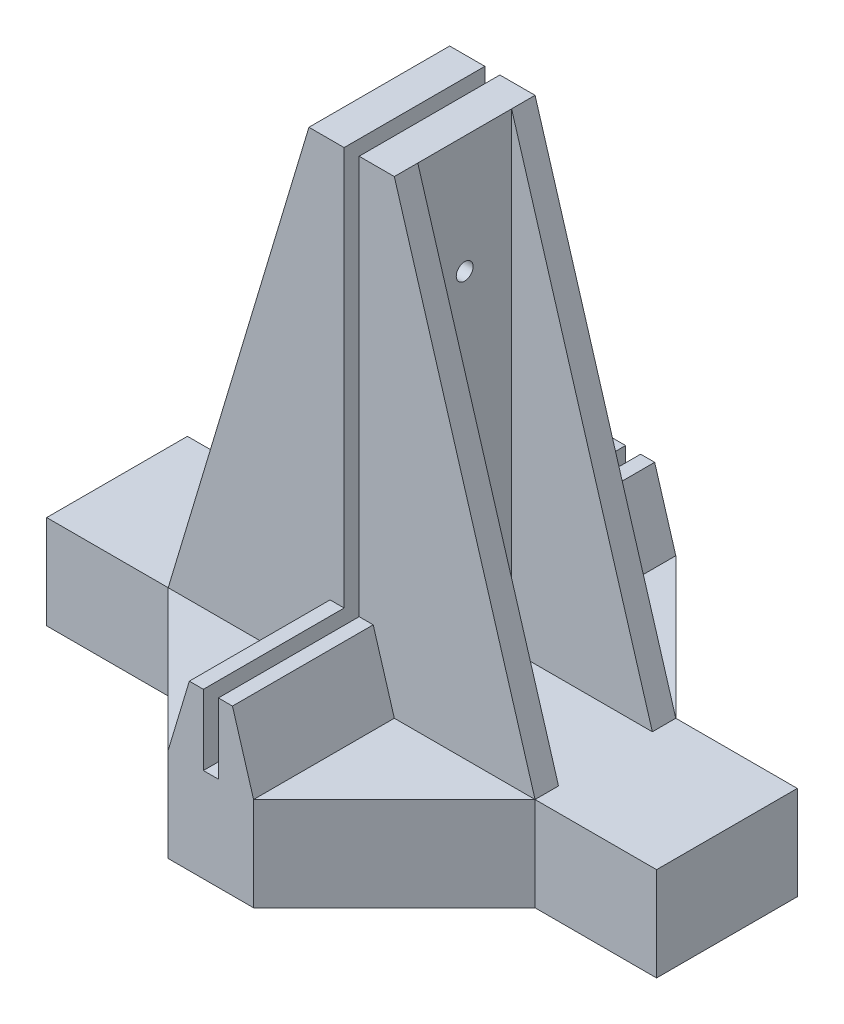
SolidWorks part; units mm, degrees
ref_plane "Front Plane" through (0, 0, 0) normal (0, 0, 1) x (1, 0, 0)
ref_plane "Top Plane" through (0, 0, 0) normal (0, 1, 0) x (1, 0, 0)
ref_plane "Right Plane" through (0, 0, 0) normal (1, 0, 0) x (0, 0, -1)
sketch "Sketch1" plane through (0, 0, 0) normal (0, 0, 1) x (1, 0, 0)
  line L0 (0, 0) -> (65, 0)
  line L1 (41.25, 0) -> (-41.25, 0) construction
  line L2 (65, 0) -> (65, 20)
  line L3 (65, 20) -> (9.1, 20)
  line L4 (9.1, 20) -> (9.1, 120)
  line L5 (9.1, 120) -> (1.6, 120)
  line L6 (1.6, 120) -> (1.6, 20)
  line L7 (1.6, 20) -> (-1.6, 20)
  line L8 (-1.6, 20) -> (-1.6, 120)
  line L9 (-1.6, 120) -> (-9.1, 120)
  line L10 (-9.1, 120) -> (-9.1, 20)
  line L11 (-9.1, 20) -> (-65, 20)
  line L12 (-65, 20) -> (-65, 0)
  line L13 (-65, 0) -> (0, 0)
  dimension "D1" = 65
  dimension "D2" = 20
  dimension "D3" = 55.9
  dimension "D4" = 100
  dimension "D5" = 7.5
  dimension "D6" = 3.2
  dimension "D7" = 130
  dimension "D8" = 7.5
extrude "Boss-Extrude3" add sketch "Sketch1" along normal blind 30
sketch "Sketch3" plane through (9.1, 0, 0) normal (1, 0, 0) x (0, 0, -1)
  line L0 (-30, 120) -> (0, 120) construction
  line L3 (-30, 20) -> (0, 20) construction
  circle A0 centre (-15, 95) radius 1.8
  circle A1 centre (-15, 45) radius 1.8
  point P0 (-15, 120)
  point P8 (0, 0)
  point P11 (0, 0)
  point P14 (0, 0)
  dimension "D3" = 3.6
  dimension "D2" = 3.6
  dimension "D4" = 25
  dimension "D1" = 50
extrude "Cut-Extrude1" cut sketch "Sketch3" against normal blind 161 and the other way blind 88
sketch "Sketch4" plane through (0, 0, 0) normal (0, 0, 1) x (1, 0, 0)
  line L0 (9.1, 120) -> (39.1, 20)
  line L1 (65, 20) -> (9.1, 20) construction
  line L2 (39.1, 20) -> (9.1, 20)
  line L3 (9.1, 20) -> (9.1, 120)
  line L4 (0, -1000) -> (0, 49000) construction
  line L6 (-9.1, 20) -> (-9.1, 120)
  line L7 (-39.1, 20) -> (-9.1, 20)
  line L8 (-9.1, 120) -> (-39.1, 20)
  dimension "D1" = 30
extrude "Boss-Extrude4" add sketch "Sketch4" along normal blind 5
extrude "Boss-Extrude5" add sketch "Sketch4<2>" against normal blind 5 from surface starting at face at (0, 50, 30)
sketch "Sketch4<2>" plane through (0, 0, 0) normal (0, 0, 1) x (1, 0, 0) same geometry as "Sketch4"
sketch "Sketch5" plane through (0, 20, 0) normal (0, 1, 0) x (1, 0, 0)
  line L0 (9.1, -25) -> (9.1, -5) construction
  line L1 (-9.1, 30) -> (9.1, 30)
  line L2 (-9.1, 30) -> (-9.1, -60) construction
  line L3 (-9.1, -60) -> (9.1, -60)
  line L4 (9.1, 30) -> (9.1, -60) construction
  line L5 (-9.1, 30) -> (9.1, -60) construction
  line L6 (-9.1, -60) -> (9.1, 30) construction
  line L7 (-9.1, -25) -> (-9.1, -5) construction
  line L8 (39.1, 0) -> (9.1, 0) construction
  line L9 (-39.1, 0) -> (-9.1, 30)
  line L10 (-39.1, 0) -> (-9.1, 0)
  line L12 (39.1, 0) -> (9.1, 30)
  line L13 (-39.1, -30) -> (-9.1, -30)
  line L14 (-39.1, -30) -> (-9.1, -60)
  line L15 (-9.1, 0) -> (-9.1, -30)
  line L16 (9.1, -60) -> (39.1, -30)
  line L17 (39.1, -30) -> (39.1, 0)
  point P0 (0, -15)
  point P5 (9.1, -15)
  dimension "D1" = 30
extrude "Boss-Extrude6" add sketch "Sketch5" against normal up to surface (20 mm away) up to face at (0, 0, 15)
sketch "Sketch7" plane through (0, 0, 30) normal (0, 0, 1) x (1, 0, 0)
  line L0 (0, -1000) -> (0, 49000) construction
  line L1 (9.1, 0) -> (-9.1, 0) construction
  line L2 (-1.6, 35) -> (-1.6, 20)
  line L3 (-1.6, 20) -> (-1.6, 120) construction
  line L4 (-1.6, 20) -> (-9.1, 20)
  line L7 (1.6, 20) -> (9.1, 20)
  line L8 (1.6, 35) -> (1.6, 20)
  line L9 (-1.6, 35) -> (-4.6, 35)
  line L10 (-4.6, 35) -> (-9.1, 20)
  line L11 (4.6, 35) -> (9.1, 20)
  line L12 (1.6, 35) -> (4.6, 35)
  point P5 (0, 0)
  dimension "D1" = 15
  dimension "D2" = 3
extrude "Boss-Extrude7" add sketch "Sketch7" along normal up to surface (30 mm away) up to face at (0, 10, 60)
extrude "Boss-Extrude8" add sketch "Sketch7<2>" along direction (0, 0, -1) on the side against the normal up to surface (60 mm away) from surface up to face at (0, 10, -30) starting at face at (12.85, 70, 0)
sketch "Sketch7<2>" plane through (0, 0, 30) normal (0, 0, 1) x (1, 0, 0) same geometry as "Sketch7"
